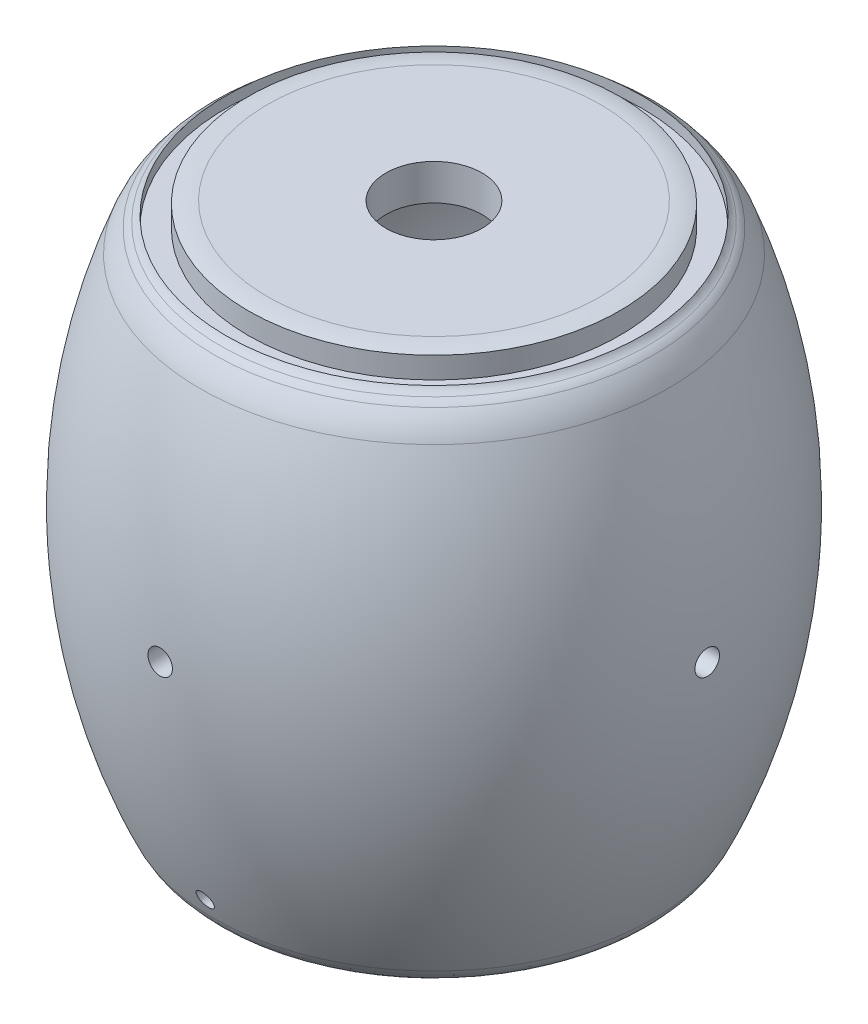
SolidWorks part; units mm, degrees
ref_plane "Front Plane" through (0, 0, 0) normal (0, 0, 1) x (1, 0, 0)
ref_plane "Top Plane" through (0, 0, 0) normal (0, 1, 0) x (1, 0, 0)
ref_plane "Right Plane" through (0, 0, 0) normal (1, 0, 0) x (0, 0, -1)
sketch "Sketch2" plane through (0, 0, 0) normal (0, 0, 1) x (1, 0, 0)
  line L1 (-142.8245, 0) -> (143.6743, 0) construction
  line L2 (-202.362, 110.7345) -> (365.1962, 110.7345) construction
  line L3 (0, -20) -> (-90, -20) construction
  line L4 (-90, -83.4454) -> (-90, 331.1943) construction
  line L8 (-20.6932, 220) -> (-90, 220)
  line L9 (-20.6932, 205) -> (-90, 205)
  line L10 (-90, 220) -> (-90, 205)
  line L11 (-4.9262, 0) -> (-19.2818, 0)
  line L12 (-19.2818, 0) -> (-19.2818, 12.4799)
  line L13 (-19.2818, 12.4799) -> (-12.1346, 13.1544)
  arc A0 (1.5112, 6.9259) -> (7.2919, 200.8089) centre (-225.9175, 110.7345) ccw
  arc A2 (1.5112, 6.9259) -> (-4.9262, 0) centre (-12.1346, 13.1544) cw
  arc A10 (-12.1346, 13.1544) -> (-12.1346, 13.1544) centre (-12.1346, 13.1544) cw
  arc A11 (-12.1346, 13.1544) -> (-6.7007, 195.4045) centre (-225.9175, 110.7345) ccw
  arc A12 (-20.6932, 205) -> (-6.7007, 195.4045) centre (-20.6932, 190) cw
  arc A17 (1.5294, 210.1533) -> (7.2919, 200.8089) centre (-20.6932, 190) cw
  arc A18 (-20.6932, 220) -> (-3.4461, 214.5466) centre (-20.6932, 190) cw
  arc A19 (-3.4461, 214.5466) -> (-1.0214, 212.1769) centre (2.1016, 217.7977) ccw
  arc A20 (-20.6932, 220) -> (7.2919, 200.8089) centre (-20.6932, 190) cw construction
  arc A21 (1.5294, 210.1533) -> (-1.0214, 212.1769) centre (-5.8781, 203.4355) ccw
  point P11 (-86.4792, 156.5384)
  point P13 (-4.944, -0.0828)
  point P14 (0, 0)
  point P30 (-6.5748, 7.2962)
  point P31 (-86.4792, 156.5384)
  point P32 (-89.8547, -12.7145)
  point P50 (0, 211.7207)
  point P51 (-198.3178, 259.5466)
  point P52 (-11.6501, 294.9746)
  point P53 (-13.1897, 216.7966)
  dimension "D3" = 250
  dimension "D7" = 15
  dimension "D1" = 30
  dimension "D4" = 220
  dimension "D12" = 10
  dimension "D2" = 90
  dimension "D5" = 20
revolve "Revolve1" add sketch "Sketch2" angle 360 about L4 region at (-12.396, 216.2413, 0)
sketch "Sketch3" plane through (0, 0, 0) normal (0, -1, 0) x (1, 0, 0)
  circle A0 centre (-90, 0) radius 77.5012
  circle A1 centre (-90, 0) radius 81
  dimension "D1" = 155.0025
  dimension "D2" = 162
extrude "Cut-Extrude1" cut sketch "Sketch3" against normal blind 20
revolve "Revolve2" add sketch "Sketch2<3>" angle 360 about L4 region at (-12.396, 216.2413, 0)
sketch "Sketch2<3>" plane through (0, 0, 0) normal (0, 0, 1) x (1, 0, 0) same geometry as "Sketch2"
ref_plane "Plane1" through (0, 0, 91.7) normal (0, 0, 1) x (1, 0, 0)
sketch "Sketch5" plane through (0, 220, 0) normal (0, 1, 0) x (1, 0, 0)
  circle A0 centre (-90, 0) radius 20
  dimension "D1" = 40
extrude "Cut-Extrude3" cut sketch "Sketch5" against normal blind 20
sketch "Sketch6" plane through (0, 0, 91.7) normal (0, 0, 1) x (1, 0, 0)
  line L0 (-90, 0) -> (-90, 330) construction
  line L1 (-175.0738, 0) -> (-4.9262, 0) construction
  line L2 (-204.0825, 110.7345) -> (38.389, 110.7345) construction
  arc A0 (-187.2919, 200.8089) -> (-181.5112, 6.9259) centre (45.9175, 110.7345) ccw construction
  circle A1 centre (-90, 110.7345) radius 5.1
  dimension "D1" = 10.2
extrude "Cut-Extrude4" cut sketch "Sketch6" against normal blind 410 and the other way blind 30
sketch "Sketch7" plane through (0, 0, 0) normal (1, 0, 0) x (0, 0, -1)
  line L0 (0, 330) -> (0, 0) construction
  line L1 (-113.8915, 110.7345) -> (113.402, 110.7345) construction
  circle A0 centre (-0.2448, 110.7345) radius 5.1
  dimension "D1" = 10.2
extrude "Cut-Extrude5" cut sketch "Sketch7" against normal through all both and the other way through all
sketch "Sketch8" plane through (0, 0, 91.7) normal (0, 0, 1) x (1, 0, 0)
  line L0 (-90, 0) -> (-90, 330) construction
  line L1 (-175.0738, 0) -> (-4.9262, 0) construction
  circle A0 centre (-90, 15.6297) radius 3.55
  dimension "D1" = 7.1
extrude "Cut-Extrude6" cut sketch "Sketch8" against normal blind 12 and the other way through all
sketch "Sketch9" plane through (0, 220, 0) normal (0, 1, 0) x (1, 0, 0)
  circle A0 centre (-90, 0) radius 86.5539
  circle A1 centre (-90, 0) radius 77.3139
  dimension "D1" = 9.24
extrude "Cut-Extrude7" cut sketch "Sketch9" against normal blind 10
